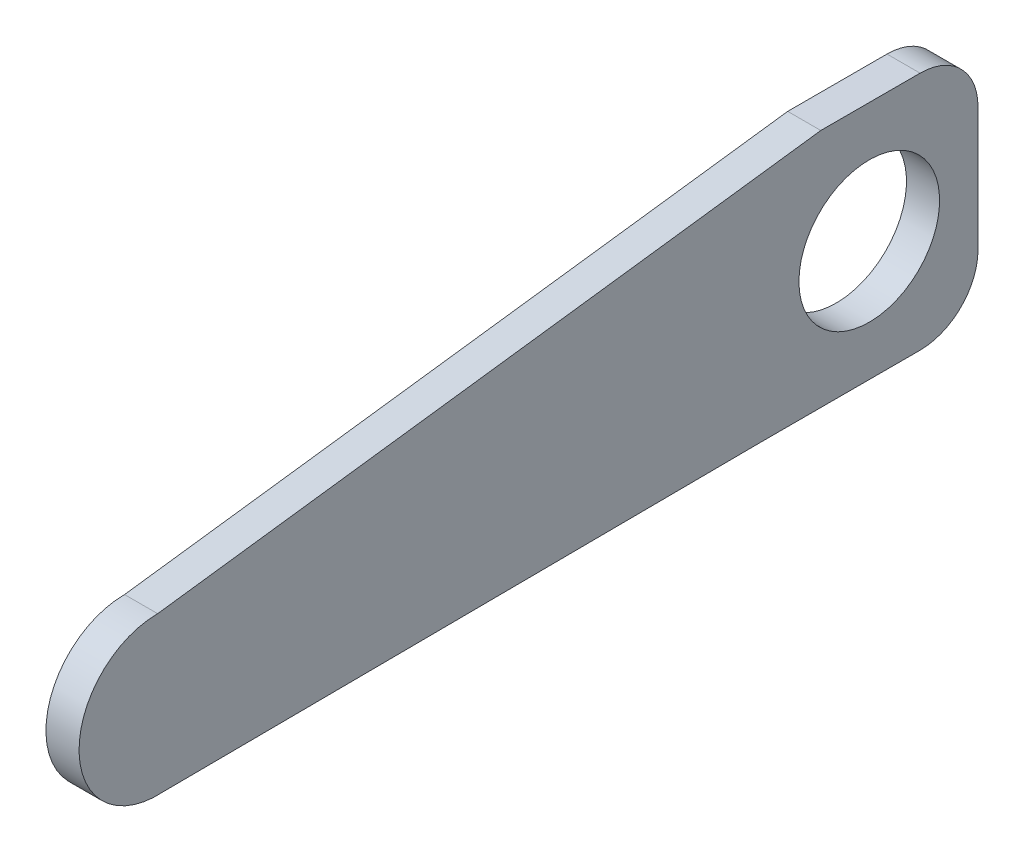
SolidWorks part; units mm, degrees
ref_plane "Front Plane" through (0, 0, 0) normal (0, 0, 1) x (1, 0, 0)
ref_plane "Top Plane" through (0, 0, 0) normal (0, 1, 0) x (1, 0, 0)
ref_plane "Right Plane" through (0, 0, 0) normal (1, 0, 0) x (0, 0, -1)
ref_plane "Plane2" through (-120, 0, 0) normal (-1, 0, 0) x (0, 0, 1)
sketch "Sketch1" plane through (-120, 0, 0) normal (-1, 0, 0) x (0, 0, 1)
  line L0 (-8.5, -5.5) -> (30.5, -5.5) construction
  line L1 (11.5361, -14.9849) -> (-61.8571, -14.5)
  line L8 (-69.1429, 14.5) -> (11, 4)
  line L9 (-100, -15) -> (-50, -15) construction
  line L10 (-61.8571, -14.5) -> (-81.1429, -14.5)
  line L12 (-69.1429, 14.5) -> (-81.1429, 14.5)
  line L13 (-88.1429, -7.5) -> (-88.1429, 7.5)
  line L14 (-61.8571, -14.5) -> (-88.1429, 14.5) construction
  line L15 (-62.6305, 13.6468) -> (-88.1429, -14.5) construction
  line L16 (-100, 18) -> (-100, -15) construction
  arc A1 (11.5361, -14.9849) -> (11, 4) centre (11, -5.5) ccw
  circle A3 centre (-75, 0) radius 8.5
  circle A5 centre (11, -5.5) radius 8.5 construction
  arc A6 (-81.1429, 14.5) -> (-88.1429, 7.5) centre (-81.1429, 7.5) ccw
  arc A7 (-81.1429, -14.5) -> (-88.1429, -7.5) centre (-81.1429, -7.5) cw
  point P9 (0, 0)
  point P10 (7.3676, -13.7344)
  point P13 (0, 0)
  point P24 (0, 0)
  point P28 (11.5107, -14.5345)
  dimension "D1" = 19
  dimension "D2" = 7
  dimension "D3" = 17
  dimension "D5" = 17
  dimension "D4" = 7
  dimension "D6" = 29
  dimension "D7" = 0.5
  dimension "D8" = 12
  dimension "D9" = 11.8571
extrude "Boss-Extrude1" add sketch "Sketch1" along normal blind 4
